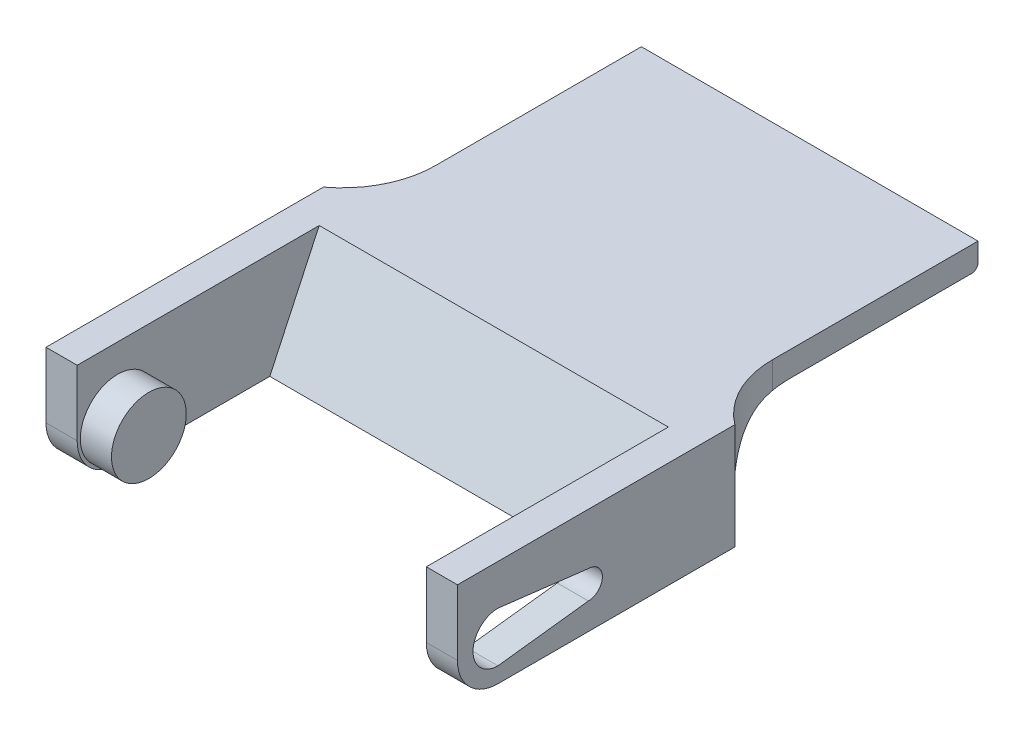
SolidWorks part; units mm, degrees
ref_plane "Front Plane" through (0, 0, 0) normal (0, 0, 1) x (1, 0, 0)
ref_plane "Top Plane" through (0, 0, 0) normal (0, 1, 0) x (1, 0, 0)
ref_plane "Right Plane" through (0, 0, 0) normal (1, 0, 0) x (0, 0, -1)
sketch "Sketch1" plane through (0, 0, 0) normal (0, 1, 0) x (1, 0, 0)
  line L1 (0, 0) -> (54, 0)
  line L2 (0, 0) -> (0, 60)
  line L3 (0, 60) -> (54, 60)
  line L4 (54, 0) -> (54, 60)
  dimension "D1" = 54
  dimension "D2" = 60
extrude "Boss-Extrude1" add sketch "Sketch1" along normal blind 4
sketch "Sketch2" plane through (54, 0, 0) normal (1, 0, 0) x (0, 0, -1)
  line L1 (0, 4) -> (10, 4)
  line L2 (0, 4) -> (0, -13)
  line L3 (0, -13) -> (10, -13)
  line L4 (10, 4) -> (10, -13)
  dimension "D1" = 17
  dimension "D2" = 10
extrude "Boss-Extrude2" add sketch "Sketch2" along normal blind 6 and the other way blind 60
sketch "Sketch3" plane through (60, 0, 0) normal (1, 0, 0) x (0, 0, -1)
  line L0 (0, 4) -> (0, -13) construction
  line L1 (0, 0) -> (-28, 0)
  line L2 (0, 0) -> (0, -13)
  line L3 (0, -13) -> (-28, -13)
  line L4 (-28, 0) -> (-28, -13)
  line L5 (10, 4) -> (0, 4) construction
  line L6 (0, -13) -> (10, -13) construction
  dimension "D1" = 4
  dimension "D2" = 0
  dimension "D3" = 28
extrude "Boss-Extrude3" add sketch "Sketch3" against normal through all
sketch "Sketch9" plane through (0, 0, 0) normal (0, 1, 0) x (1, 0, 0)
  line L0 (-6, -28) -> (60, -28) construction
  line L1 (-1, 0) -> (55, 0)
  line L2 (-1, 0) -> (-1, -28)
  line L3 (-1, -28) -> (55, -28)
  line L4 (55, 0) -> (55, -28)
  line L6 (-6, 0) -> (-6, -28) construction
  line L7 (60, 0) -> (60, -28) construction
  dimension "D1" = 5
  dimension "D2" = 5
extrude "Cut-Extrude3" cut sketch "Sketch9" against normal blind 13
sketch "Sketch10" plane through (0, 0, 0) normal (0, 1, 0) x (1, 0, 0)
  line L0 (60, 0) -> (60, -28) construction
  line L1 (-6, -28) -> (-1, -28)
  line L2 (-6, -28) -> (-6, 0)
  line L3 (-6, 0) -> (-1, 0)
  line L4 (-1, -28) -> (-1, 0)
  line L5 (55, 0) -> (60, 0)
  line L6 (55, 0) -> (55, -28)
  line L7 (55, -28) -> (60, -28)
  line L8 (60, 0) -> (60, -28)
  line L9 (55, -28) -> (60, -28) construction
  dimension "D1" = 0
extrude "Boss-Extrude6" add sketch "Sketch10" along normal blind 4
sketch "Sketch11" plane through (60, 0, 0) normal (1, 0, 0) x (0, 0, -1)
  line L0 (-28, -13) -> (10, -13) construction
  line L1 (10, -13) -> (10, 4) construction
  line L2 (-23, -2.5) -> (-8.5, -4.25)
  line L3 (-8.5, -8.75) -> (-23, -10.5)
  circle A0 centre (-23, -6.5) radius 4
  circle A1 centre (-8.5, -6.5) radius 2.25
  dimension "D1" = 8
  dimension "D2" = 6.5
  dimension "D3" = 33
  dimension "D4" = 4.5
  dimension "D5" = 14.5
  dimension "D6" = 6.5
extrude "Cut-Extrude5" cut sketch "Sketch11" against normal through all contours L2 A0 L3 | A1 L2 A0 L3 | A1 A0 region at (60, -6.5, 23.0004) region at (60, -6.5, 15.2652) region at (60, -6.5, 8.5)
sketch "Sketch12" plane through (0, 0, 28) normal (0, 0, 1) x (1, 0, 0)
  line L1 (60, 4) -> (55, 4)
  line L2 (60, 4) -> (60, -13)
  line L3 (60, -13) -> (55, -13)
  line L4 (55, 4) -> (55, -13)
  line L5 (-1, 4) -> (-6, 4)
  line L6 (-1, 4) -> (-1, -13)
  line L7 (-1, -13) -> (-6, -13)
  line L8 (-6, 4) -> (-6, -13)
extrude "Boss-Extrude7" add sketch "Sketch12" along normal blind 4
sketch "Sketch13" plane through (-6, 0, 0) normal (-1, 0, 0) x (0, 0, 1)
  line L0 (29.5, -6.5) -> (29.5, 4)
  line L1 (-10, 4) -> (32, 4) construction
  line L2 (29.5, 4) -> (32, 4)
  line L3 (32, 4) -> (32, -13)
  line L4 (32, -13) -> (23, -13)
  arc A0 (23, -13) -> (29.5, -6.5) centre (23, -6.5) ccw
extrude "Cut-Extrude6" cut sketch "Sketch13" against normal through all
fillet "Fillet3" radius 1 1 edges at (27, 0, -60)
sketch "Sketch14" plane through (-1, 0, 0) normal (1, 0, 0) x (0, 0, -1)
  circle A0 centre (-23, -6.5) radius 4
extrude "Boss-Extrude8" add sketch "Sketch14" along normal blind 10 and the other way blind 5
sketch "Sketch15" plane through (-1, 0, 0) normal (1, 0, 0) x (0, 0, -1)
  line L0 (0, -13) -> (-23, -13) construction
  line L1 (-23, -10.5) -> (-6, -10.5)
  line L2 (-23, -10.5) -> (-23, -2.5)
  line L3 (-23, -2.5) -> (-6, -2.5)
  line L4 (-6, -10.5) -> (-6, -2.5)
  arc A0 (-22.0483, -2.6149) -> (-22.0483, -10.3851) centre (-23, -6.5) ccw construction
  dimension "D1" = 8
  dimension "D2" = 17
  dimension "D3" = 2.5
extrude "Boss-Extrude9" add sketch "Sketch15" against normal blind 5
sketch "Sketch16" plane through (9, 0, 0) normal (1, 0, 0) x (0, 0, -1)
  circle A0 centre (-23, -6.5) radius 6
  dimension "12" = 12
extrude "Boss-Extrude11" add sketch "Sketch16" against normal blind 12
sketch "Sketch17" plane through (9, 0, 0) normal (1, 0, 0) x (0, 0, -1)
  circle A0 centre (-23, -6.5) radius 6
extrude "Cut-Extrude7" cut sketch "Sketch17" against normal blind 5
chamfer "Chamfer1" distance 20 angle 25 1 edges at (27, 4, 0) first distance on face at (27, -4.5, 0)
sketch "Sketch18" plane through (0, 4, 0) normal (0, 1, 0) x (1, 0, 0)
  line L10 (-6, 10) -> (60, 10)
  line L11 (-6, 10) -> (-6, 15)
  line L12 (-6, 15) -> (60, 15)
  line L13 (60, 10) -> (60, 15)
  dimension "D1" = 5
extrude "Boss-Extrude14" add sketch "Sketch18" against normal blind 17
fillet "Fillet8" radius 15 1 edges at (27, 0, -15)
fillet "Fillet9" radius 15 2 edges at (54, -4.5, -15) (0, -4.5, -15)
